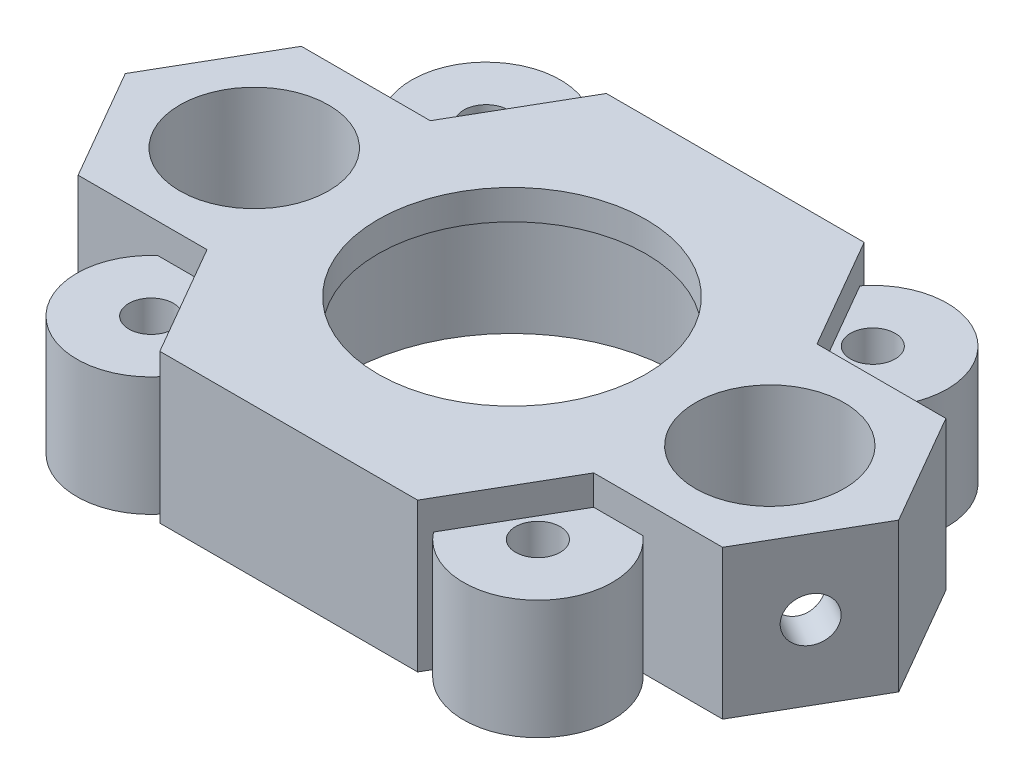
SolidWorks part; units mm, degrees
ref_plane "Front Plane" through (0, 0, 0) normal (0, 0, 1) x (1, 0, 0)
ref_plane "Top Plane" through (0, 0, 0) normal (0, 1, 0) x (1, 0, 0)
ref_plane "Right Plane" through (0, 0, 0) normal (1, 0, 0) x (0, 0, -1)
sketch "Sketch1" plane through (0, 0, 0) normal (0, 1, 0) x (1, 0, 0)
  line L0 (0, 0) -> (17.3205, 0) construction
  line L1 (17.3205, 0) -> (14.8205, 4.3301) construction
  line L2 (8.6603, 15) -> (-8.6603, 15)
  line L3 (-8.6603, 15) -> (-9.049, 14.3266)
  line L4 (-9.049, -14.3266) -> (-8.6603, -15)
  line L5 (-8.6603, -15) -> (8.6603, -15)
  line L6 (8.6603, -15) -> (9.049, -14.3266)
  line L7 (0, 15) -> (0, -15) construction
  line L8 (25.9808, 0) -> (21.6506, 7.5)
  line L9 (21.6506, 7.5) -> (16.2976, 7.5)
  line L10 (10.8253, 3.75) -> (10.6036, 3.3659)
  line L11 (10.6036, -3.3659) -> (10.8253, -3.75) construction
  line L12 (16.2976, -7.5) -> (21.6506, -7.5)
  line L13 (21.6506, -7.5) -> (25.9808, 0)
  line L14 (-21.6506, -7.5) -> (-25.9808, 0)
  line L15 (-16.2976, -7.5) -> (-21.6506, -7.5)
  line L16 (-10.6036, -3.3659) -> (-12.9904, -7.5) construction
  line L17 (-12.9904, 7.5) -> (-10.6036, 3.3659) construction
  line L18 (-21.6506, 7.5) -> (-16.2976, 7.5)
  line L19 (-25.9808, 0) -> (-21.6506, 7.5)
  line L20 (-12.9904, 7.5) -> (-14.8205, 4.3301) construction
  line L21 (-14.8205, 4.3301) -> (-17.3205, 0) construction
  line L22 (-17.3205, 0) -> (-14.8205, -4.3301) construction
  line L23 (-10.6036, 3.3659) -> (-8.6603, 0) construction
  line L24 (-8.6603, 0) -> (-10.6036, -3.3659) construction
  line L25 (-14.8205, -4.3301) -> (-12.9904, -7.5) construction
  line L26 (10.6036, 3.3659) -> (8.6603, 0) construction
  line L27 (8.6603, 0) -> (10.6036, -3.3659) construction
  line L28 (10.8253, -3.75) -> (12.9904, -7.5) construction
  line L29 (14.8205, 4.3301) -> (13.5705, 6.4952) construction
  line L30 (9.049, 14.3266) -> (8.6603, 15)
  line L31 (13.5705, -6.4952) -> (14.8205, -4.3301) construction
  line L32 (14.8205, -4.3301) -> (17.3205, 0) construction
  line L33 (12.9904, -7.5) -> (13.5705, -6.4952) construction
  line L34 (12.9904, 7.5) -> (10.8253, 3.75) construction
  line L35 (13.5705, 6.4952) -> (12.9904, 7.5) construction
  line L36 (-12.9904, 7.5) -> (-12.9904, 15) construction
  line L37 (-12.9904, 15) -> (-8.6603, 15) construction
  line L38 (-9.049, 14.3266) -> (-12.9904, 7.5) construction
  line L39 (-16.2976, 7.5) -> (-12.9904, 7.5) construction
  line L40 (-55, 0) -> (55, 0) construction
  line L41 (-12.9904, -7.5) -> (-9.049, -14.3266) construction
  line L42 (-12.9904, -7.5) -> (-16.2976, -7.5) construction
  line L43 (9.049, -14.3266) -> (12.9904, -7.5) construction
  line L44 (12.9904, -7.5) -> (16.2976, -7.5) construction
  line L45 (16.2976, 7.5) -> (12.9904, 7.5) construction
  line L46 (12.9904, 7.5) -> (9.049, 14.3266) construction
  circle A0 centre (0, 0) radius 11.125
  circle A1 centre (0, 0) radius 15 construction
  circle A2 centre (17.3205, 0) radius 5
  circle A3 centre (17.3205, 0) radius 7.5 construction
  circle A4 centre (-17.3205, 0) radius 5
  arc A5 (-9.049, 14.3266) -> (-16.2976, 7.5) centre (-12.9904, 11.25) ccw
  circle A6 centre (-12.9904, 11.25) radius 1.5
  arc A7 (-12.2966, 6.2984) -> (-8.1704, 12.5795) centre (-12.9904, 11.25) ccw construction
  arc A8 (-8.1704, 12.5795) -> (-9.049, 14.3266) centre (-12.9904, 11.25) ccw construction
  arc A9 (-13.6177, 6.2895) -> (-12.2966, 6.2984) centre (-12.9904, 11.25) ccw construction
  arc A10 (-13.6841, 6.2984) -> (-13.6177, 6.2895) centre (-12.9904, 11.25) ccw construction
  arc A11 (-16.2976, 7.5) -> (-13.6841, 6.2984) centre (-12.9904, 11.25) ccw construction
  circle A12 centre (12.9904, 11.25) radius 1.5
  arc A13 (9.049, 14.3266) -> (16.2976, 7.5) centre (12.9904, 11.25) cw
  circle A14 centre (12.9904, -11.25) radius 1.5
  arc A15 (9.049, -14.3266) -> (16.2976, -7.5) centre (12.9904, -11.25) ccw
  circle A16 centre (-12.9904, -11.25) radius 1.5
  arc A17 (-9.049, -14.3266) -> (-16.2976, -7.5) centre (-12.9904, -11.25) cw
  dimension "D1" = 22.25
  dimension "D3" = 10
  dimension "D6" = 10
  dimension "D7" = 3
  dimension "D2" = 30
  dimension "D4" = 15
  dimension "D5" = 90
extrude "Boss-Extrude1" add sketch "Sketch1" along normal blind 8 contours A6 | A12 | A14 | A16 | L30 L2 L3 A5 L18 L19 L14 L15 A17 L4 L5 L6 A15 L12 L13 L8 L9 A13 | A0 | A4 | A2 region at (-12.9904, 0, -11.25) region at (12.9904, 0, -11.25) region at (12.9904, 0, 11.25) region at (-12.9904, 0, 11.25)
sketch "Sketch2" plane through (0, 8, 0) normal (0, 1, 0) x (1, 0, 0)
  line L0 (-8.6603, 15) -> (-12.9904, 7.5)
  line L1 (-12.9904, 7.5) -> (-21.6506, 7.5)
  line L2 (-21.6506, 7.5) -> (-25.9808, 0)
  line L3 (-25.9808, 0) -> (-21.6506, -7.5)
  line L6 (-21.6506, -7.5) -> (-12.9904, -7.5)
  line L7 (-12.9904, -7.5) -> (-8.6603, -15)
  line L8 (-8.6603, -15) -> (8.6603, -15)
  line L9 (8.6603, -15) -> (12.9904, -7.5)
  line L10 (12.9904, -7.5) -> (21.6506, -7.5)
  line L11 (21.6506, -7.5) -> (25.9808, 0)
  line L12 (25.9808, 0) -> (21.6506, 7.5)
  line L13 (21.6506, 7.5) -> (12.9904, 7.5)
  line L14 (12.9904, 7.5) -> (8.6603, 15)
  line L15 (8.6603, 15) -> (-8.6603, 15)
  line L16 (21.6506, 7.5) -> (16.2976, 7.5) construction
  line L17 (21.6506, -7.5) -> (25.9808, 0) construction
  line L18 (-8.6603, -15) -> (8.6603, -15) construction
  line L19 (-21.6506, -7.5) -> (-25.9808, 0) construction
  circle A0 centre (0, 0) radius 9
  circle A1 centre (-17.3205, 0) radius 5
  circle A2 centre (17.3205, 0) radius 5
  circle A5 centre (-17.3205, 0) radius 5 construction
  circle A6 centre (17.3205, 0) radius 5 construction
  point P2 (8.6603, -15)
  point P9 (-25.9808, 0)
  point P10 (-21.6506, -7.5)
  point P11 (0, 0)
  point P12 (0, 0)
  point P19 (12.9904, -7.5)
  point P21 (0, 0)
  point P22 (-8.6603, -15)
  point P25 (0, 0)
  point P27 (-25.9808, 0)
  point P44 (0, 0)
  point P45 (0, 0)
  point P46 (0, 0)
  point P47 (0, 0)
  point P48 (-8.6603, 15)
  point P50 (0, 0)
  point P51 (8.6603, 15)
  point P53 (0, 0)
  point P54 (21.6506, 7.5)
  point P57 (25.9808, 0)
  point P60 (0, 0)
  point P61 (21.6506, -7.5)
  point P63 (0, 0)
  point P64 (0, 0)
  point P66 (0, 0)
  point P67 (-21.6506, 7.5)
  point P69 (-25.9686, 0)
  point P70 (-21.6506, 7.5)
  point P71 (-21.6506, 7.5)
  point P72 (-12.9904, 7.5)
  point P73 (-17.3205, 0)
  point P74 (-25.9808, 0)
  dimension "D1" = 18
  dimension "D3" = 8.6603
  dimension "D2" = 8.6603
  dimension "D4" = 8.6603
  dimension "D5" = 8.6603
  dimension "D6" = 8.6603
extrude "Boss-Extrude2" add sketch "Sketch2" along normal blind 2
sketch "Sketch4" plane through (-19.4856, 0, 11.25) normal (-0.866, 0, 0.5) x (0.5, 0, 0.866)
  line L0 (-8.6603, 10) -> (-8.6603, 0) construction
  line L1 (-12.9904, 10) -> (-4.3301, 10) construction
  line L3 (-12.9904, 5) -> (-4.3301, 5) construction
  line L4 (-12.9904, 10) -> (-12.9904, 0) construction
  line L5 (-4.3301, 10) -> (-4.3301, 0) construction
  circle A0 centre (-8.6603, 5) radius 1.5
  point P4 (-8.6603, 0)
  point P14 (0, 0)
  dimension "D1" = 3
extrude "Cut-Extrude1" cut sketch "Sketch4" against normal up to surface and the other way through all up to face at (-17.3205, 0, -5)
sketch "Sketch5" plane through (19.4856, 0, 11.25) normal (0.866, 0, 0.5) x (0.5, 0, -0.866)
  line L0 (8.6603, 10) -> (8.6603, 0) construction
  line L1 (4.3301, 10) -> (12.9904, 10) construction
  line L3 (4.3301, 5) -> (12.9904, 5) construction
  line L4 (4.3301, 10) -> (4.3301, 0) construction
  line L5 (12.9904, 10) -> (12.9904, 0) construction
  line L6 (4.3301, 0) -> (12.9904, 0) construction
  circle A0 centre (8.6603, 5) radius 1.5
  point P4 (8.6603, 0)
  point P14 (0, 0)
  dimension "D1" = 3
extrude "Cut-Extrude2" cut sketch "Sketch5" against normal up to surface (2.7303 mm away) up to face at (17.3205, 0, 5)
